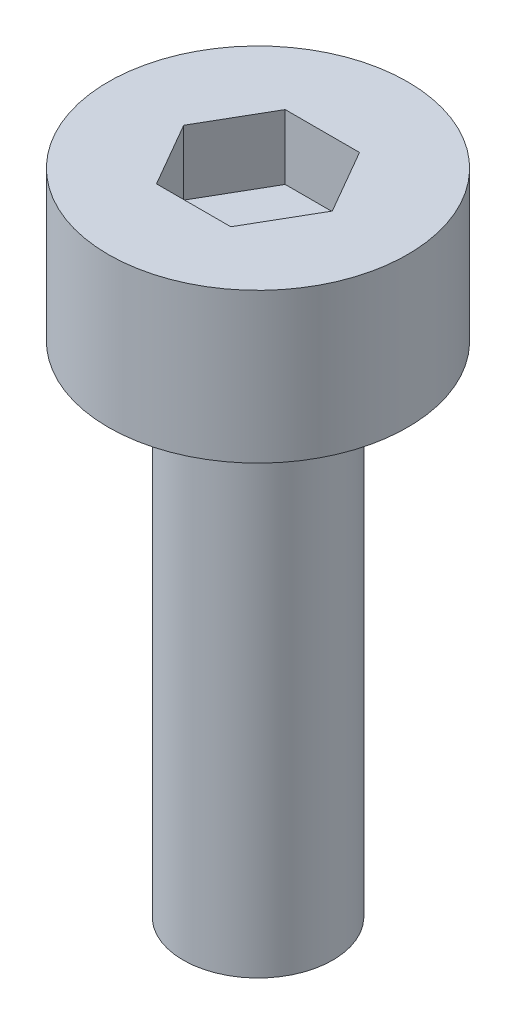
SolidWorks part; units mm, degrees
ref_plane "Front Plane" through (0, 0, 0) normal (0, 0, 1) x (1, 0, 0)
ref_plane "Top Plane" through (0, 0, 0) normal (0, 1, 0) x (1, 0, 0)
ref_plane "Right Plane" through (0, 0, 0) normal (1, 0, 0) x (0, 0, -1)
sketch "Sketch1" plane through (0, 0, 0) normal (0, 1, 0) x (1, 0, 0)
  circle A0 centre (0, 0) radius 1.5
  dimension "D1" = 3
extrude "ScrewShaft" add sketch "Sketch1" along normal blind 10
sketch "Sketch2" plane through (0, 10, 0) normal (0, 1, 0) x (1, 0, 0)
  circle A0 centre (0, 0) radius 3
  dimension "D1" = 6
extrude "Boss-Extrude2" add sketch "Sketch2" along normal blind 3
sketch "Sketch3" plane through (0, 13, 0) normal (0, 1, 0) x (1, 0, 0)
  line L0 (0, 0) -> (0, 1.29) construction
  line L1 (1.4896, 0) -> (0.7448, 1.29)
  line L2 (0.7448, 1.29) -> (-0.7448, 1.29)
  line L3 (-0.7448, 1.29) -> (-1.4896, 0)
  line L4 (-1.4896, 0) -> (-0.7448, -1.29)
  line L5 (-0.7448, -1.29) -> (0.7448, -1.29)
  line L6 (0.7448, -1.29) -> (1.4896, 0)
  circle A0 centre (0, 0) radius 1.29 construction
  dimension "D1" = 2.58
extrude "Cut-Extrude1" cut sketch "Sketch3" against normal blind 1.3
equation "\"X-ROD-SPACING\"=45"
equation "\"Y-ROD-SPACING\"=75"
equation "\"Z-ROD-SPACING\"=17.5"
equation "\"Y-BED-OFFSET\"=2"
equation "\"Y-BED-ROD-INSET\"=3.5"
equation "\"T-SLOT-NUT-FILLET-RADIUS\"=0.5"
equation "\"T-SLOT-SCREW-SHAFT-RADIUS\"=1.55"
equation "\"T-SLOT-SCREW-SHAFT-CUTOUT-LENGTH\"=11"
equation "\"T-SLOT-NUT-DEPTH\"=3.5"
equation "\"T-SLOT-NUT-WIDTH\"=2.85"
equation "\"T-SLOT-NUT-END-DISTANCE\"=8"
equation "\"ACRYLIC-THICKNESS\"=10"
equation "\"ACRYLIC-THICKNESS2\"=4.5"
equation "\"ACRYLIC-TAB-CUTOUT-SIZE\"=\"ACRYLIC-THICKNESS\"+\"ACRYLIC-TAB-TOLERANCE\"*2"
equation "\"ACRYLIC-TAB-WIDTH\"=\"ACRYLIC-THICKNESS\""
equation "\"ACRYLIC-M3-HOLE\"=2.9"
equation "\"SMOOTHROD-CAP-SCREW-DISTANCE\"=20"
equation "\"FRAME-WIDTH-INNER\"=370"
equation "\"NEMA17-HOLE-SPACING\"=31"
equation "\"NEMA17-CENTRAL-CUTOUT\"=22.5"
equation "\"Z-BRACKET-REACH\"=55"
equation "\"TOP-BRACKET-SPACING\"=40"
equation "\"SMOOTHROD-X-LENGTH\"=350"
equation "\"SMOOTHROD-Y-LENGTH\"=350"
equation "\"SMOOTHROD-Z-LENGTH\"=350"
equation "\"SMOOTHROD-TIGHTENING-HEADROOM\"=.25"
equation "\"LEADSCREW-Z-LENGTH\"=300"
equation "\"SCREW-LENGTH-FRAME\"=\"ACRYLIC-THICKNESS\" + 10"
equation "\"SCREW-HEAD-RADIUS\"=6"
equation "\"PRINTED-X-SMOOTHROD-DIAMETER\"=9.0"
equation "\"PRINTED-X-SMOOTHROD-CUTOUT\"=10"
equation "\"PRINTED-X-BASE-HEIGHT\"=10"
equation "\"PRINTED-LM8UU-CUTOUT-SIZE\"=15.5"
equation "\"PRINTED-LM8UU-CUTOUT-LENGTH\"=24.5"
equation "\"PRINTED-X-IDLER-HEIGHT\"=16"
equation "\"PSU-MOUNTING-WIDTH\"=95"
equation "\"PSU-MOUNTING-HEIGHT\"=177"
equation "\"D1@Sketch2\"=\"SCREW-HEAD-RADIUS\""
